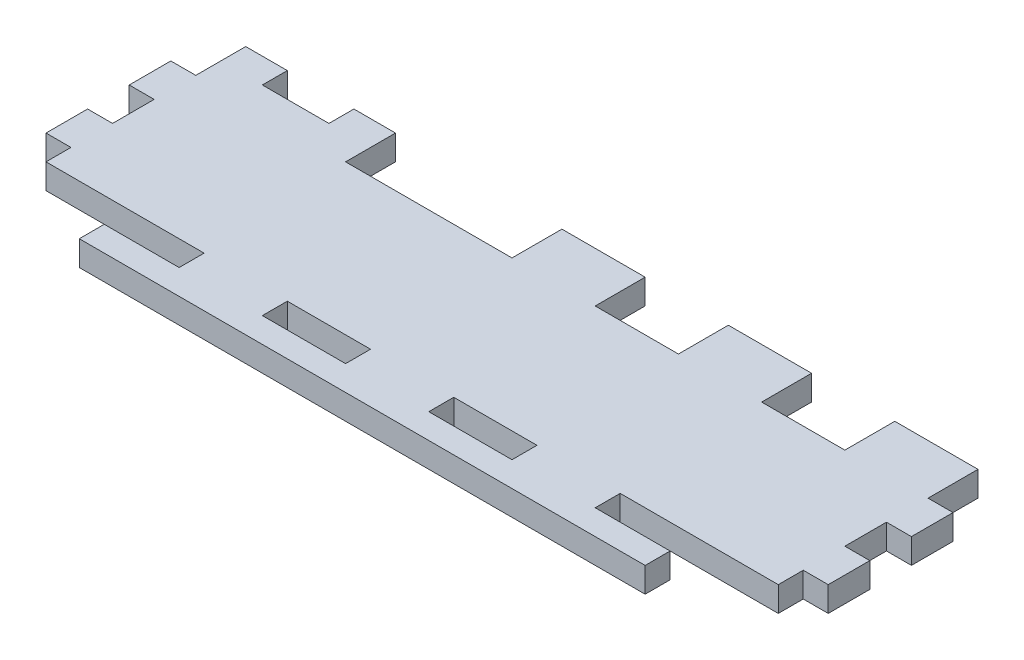
SolidWorks part; units mm, degrees
material "Maple"
ref_plane "Front Plane" through (0, 0, 0) normal (0, 0, 1) x (1, 0, 0)
ref_plane "Top Plane" through (0, 0, 0) normal (0, 1, 0) x (1, 0, 0)
ref_plane "Right Plane" through (0, 0, 0) normal (1, 0, 0) x (0, 0, -1)
sketch "Sketch1" plane through (0, 0, 0) normal (0, 1, 0) x (1, 0, 0)
  line L1 (0, 0) -> (88, 0)
  line L2 (0, 0) -> (0, -18)
  line L3 (0, -18) -> (88, -18)
  line L4 (88, 0) -> (88, -18)
  dimension "D1" = 88
  dimension "D2" = 18
extrude "Boss-Extrude1" add sketch "Sketch1" along normal blind 3
sketch "Sketch2" plane through (0, 0, 0) normal (0, -1, 0) x (1, 0, 0)
  line L0 (88, 0) -> (0, 0) construction
  line L1 (0, 0) -> (18, 0)
  line L2 (0, 0) -> (0, -3)
  line L3 (0, -3) -> (18, -3)
  line L4 (18, 0) -> (18, -3)
  line L5 (0, 0) -> (0, 18) construction
  dimension "D1" = 18
  dimension "D2" = 3
extrude "Boss-Extrude2" add sketch "Sketch2" against normal through all
sketch "Sketch3" plane through (0, 0, 0) normal (0, -1, 0) x (1, 0, 0)
  line L0 (44, 18) -> (44, 0) construction
  line L1 (0, 18) -> (88, 18) construction
  line L2 (88, 0) -> (18, 0) construction
  line L4 (39, 21) -> (49, 21)
  line L5 (39, 21) -> (39, 18)
  line L6 (39, 18) -> (49, 18)
  line L7 (49, 21) -> (49, 18)
  line L8 (39, 21) -> (49, 18) construction
  line L9 (39, 18) -> (49, 21) construction
  point P6 (44, 19.5)
  dimension "D1" = 3
  dimension "D2" = 10
extrude "Boss-Extrude3" add sketch "Sketch3" against normal through all
pattern_linear "LPattern1" count 3 spacing 20 along (1, 0, 0) count 3 spacing 20 along (-1, 0, 0) of "Boss-Extrude3" pattern seed only yes
sketch "Sketch4" plane through (0, 0, 0) normal (0, -1, 0) x (-1, 0, 0)
  line L1 (1, -21) -> (0, -21)
  line L2 (1, -21) -> (1, -18)
  line L3 (1, -18) -> (0, -18)
  line L4 (0, -21) -> (0, -18)
  line L5 (-89, -21) -> (-88, -21)
  line L6 (-89, -21) -> (-89, -18)
  line L7 (-89, -18) -> (-88, -18)
  line L8 (-88, -21) -> (-88, -18)
extrude "Cut-Extrude1" cut sketch "Sketch4" against normal through all
sketch "Sketch5" plane through (0, 0, 0) normal (0, -1, 0) x (-1, 0, 0)
  line L0 (-88, -21) -> (-88, 0) construction
  line L1 (0, -21) -> (-88, -21)
  line L2 (0, -21) -> (0, -24)
  line L3 (0, -24) -> (-88, -24)
  line L4 (-88, -21) -> (-88, -24)
  dimension "D1" = 3
extrude "Boss-Extrude4" add sketch "Sketch5" against normal through all
sketch "Sketch6" plane through (0, 0, 0) normal (0, -1, 0) x (-1, 0, 0)
  line L0 (0, 3) -> (-18, 3) construction
  line L1 (0, 3) -> (-5, 3)
  line L2 (0, 3) -> (0, 6)
  line L3 (0, 6) -> (-5, 6)
  line L4 (-5, 3) -> (-5, 6)
  line L5 (-18, 3) -> (-13, 3)
  line L6 (-18, 3) -> (-18, 6)
  line L7 (-18, 6) -> (-13, 6)
  line L8 (-13, 3) -> (-13, 6)
  dimension "D1" = 3
  dimension "D2" = 5
extrude "Boss-Extrude5" add sketch "Sketch6" against normal through all
sketch "Sketch7" plane through (0, 0, 0) normal (0, -1, 0) x (-1, 0, 0)
  line L0 (-88, 0) -> (-18, 0) construction
  line L1 (-88, 0) -> (-78, 0)
  line L2 (-88, 0) -> (-88, 6)
  line L3 (-88, 6) -> (-78, 6)
  line L4 (-78, 0) -> (-78, 6)
  dimension "D1" = 6
  dimension "D2" = 10
extrude "Boss-Extrude6" add sketch "Sketch7" against normal through all
pattern_linear "LPattern2" count 3 spacing 20 along (-1, 0, 0) of "Boss-Extrude6"
sketch "Sketch9" plane through (0, 0, 0) normal (0, -1, 0) x (-1, 0, 0)
  line L0 (0, 6) -> (0, -24) construction
  line L1 (-9, -21) -> (0, -21)
  line L2 (-9, -21) -> (-9, -18)
  line L3 (-9, -18) -> (0, -18)
  line L4 (0, -21) -> (0, -18)
  line L5 (-88, -24) -> (-88, 6) construction
  line L6 (-79, -21) -> (-88, -21)
  line L7 (-79, -21) -> (-79, -18)
  line L8 (-79, -18) -> (-88, -18)
  line L9 (-88, -21) -> (-88, -18)
  line L10 (-69, -18) -> (-79, -18) construction
  line L11 (-9, -18) -> (-19, -18) construction
extrude "Cut-Extrude2" cut sketch "Sketch9" against normal through all
sketch "Sketch10" plane through (0, 0, 0) normal (0, -1, 0) x (-1, 0, 0)
  line L0 (0, 6) -> (0, -18) construction
  line L1 (0, -15) -> (3, -15)
  line L2 (0, -15) -> (0, -10)
  line L3 (0, -10) -> (3, -10)
  line L4 (3, -15) -> (3, -10)
  line L5 (-88, -18) -> (-88, 6) construction
  line L6 (-88, -15) -> (-91, -15)
  line L7 (-88, -15) -> (-88, -10)
  line L8 (-88, -10) -> (-91, -10)
  line L9 (-91, -15) -> (-91, -10)
  line L10 (0, -18) -> (-19, -18) construction
  dimension "D1" = 3
  dimension "D2" = 3
  dimension "D3" = 5
extrude "Boss-Extrude8" add sketch "Sketch10" against normal through all
pattern_linear "LPattern4" count 2 spacing 10 along (0, 0, -1) of "Boss-Extrude8"
sketch "Sketch11" plane through (0, 0, 0) normal (0, -1, 0) x (-1, 0, 0)
  line L0 (0, -21) -> (-19, -21) construction
  line L1 (0, -24) -> (-10, -24)
  line L2 (0, -24) -> (0, -21)
  line L3 (0, -21) -> (-10, -21)
  line L4 (-10, -24) -> (-10, -21)
  line L5 (-69, -21) -> (-88, -21) construction
  line L6 (-88, -24) -> (-78, -24)
  line L7 (-88, -24) -> (-88, -21)
  line L8 (-88, -21) -> (-78, -21)
  line L9 (-78, -24) -> (-78, -21)
  dimension "D1" = 10
  dimension "D2" = 10
extrude "Cut-Extrude3" cut sketch "Sketch11" against normal through all
equation "\"D2@Sketch11\"=\"D1@Sketch11\""
